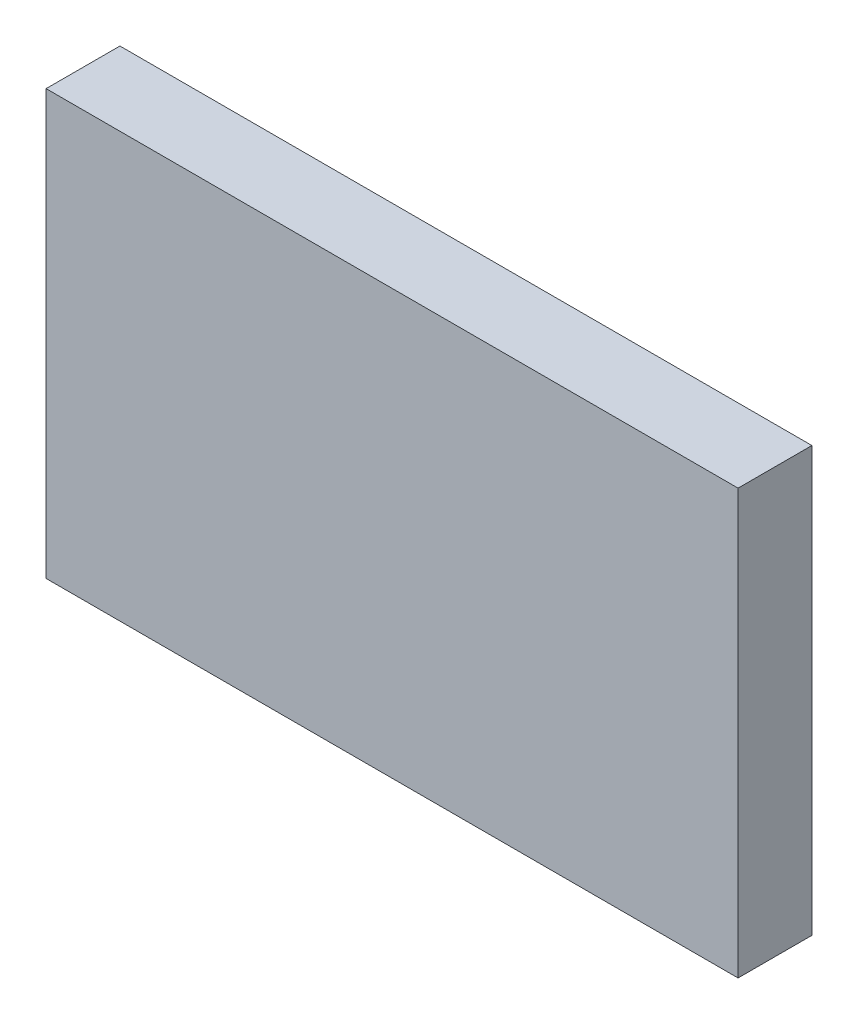
SolidWorks part; units mm, degrees
ref_plane "Front Plane" through (0, 0, 0) normal (0, 0, 1) x (1, 0, 0)
ref_plane "Top Plane" through (0, 0, 0) normal (0, 1, 0) x (1, 0, 0)
ref_plane "Right Plane" through (0, 0, 0) normal (1, 0, 0) x (0, 0, -1)
sketch "Sketch1" plane through (0, 0, 0) normal (0, 0, 1) x (1, 0, 0)
  line L1 (0, 0) -> (178.0979, 0)
  line L2 (0, 0) -> (0, 109.191)
  line L3 (0, 109.191) -> (178.0979, 109.191)
  line L4 (178.0979, 0) -> (178.0979, 109.191)
extrude "Boss-Extrude1" add sketch "Sketch1" along normal blind 19
